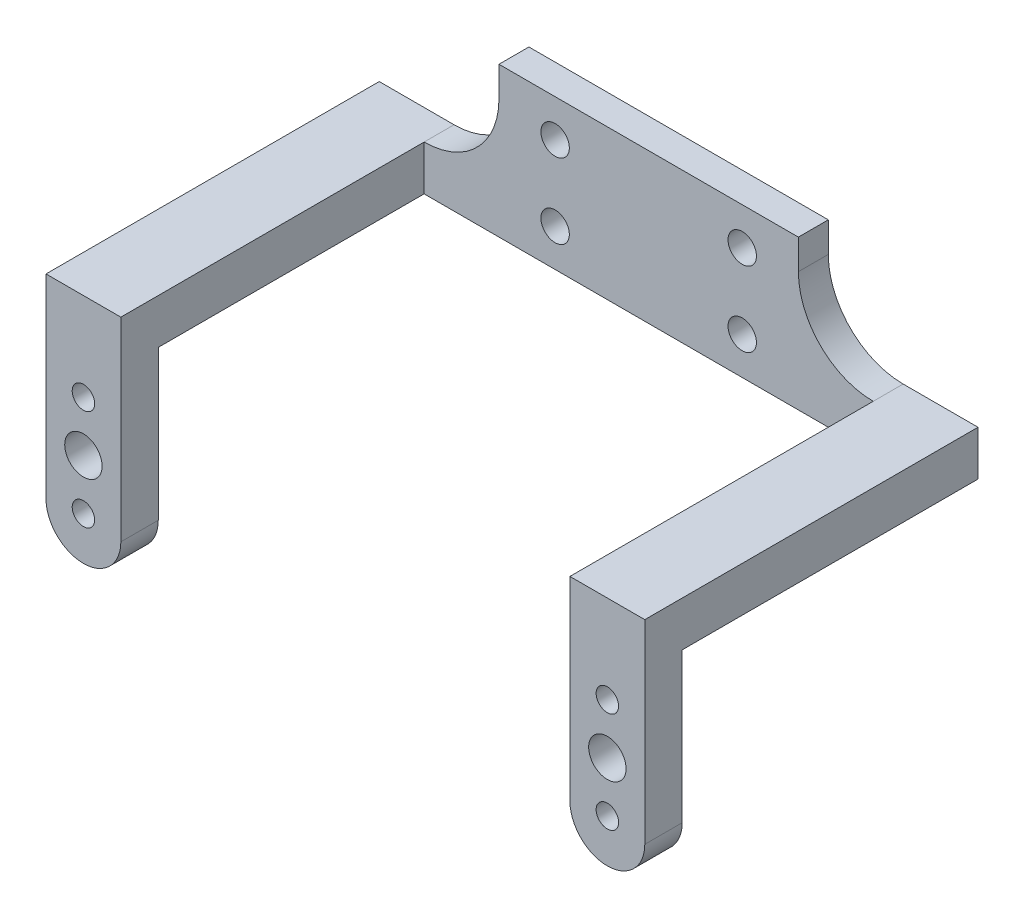
SolidWorks part; units mm, degrees
ref_plane "Front Plane" through (0, 0, 0) normal (0, 0, 1) x (1, 0, 0)
ref_plane "Top Plane" through (0, 0, 0) normal (0, 1, 0) x (1, 0, 0)
ref_plane "Right Plane" through (0, 0, 0) normal (1, 0, 0) x (0, 0, -1)
sketch "Sketch1" plane through (0, 0, 0) normal (0, 0, 1) x (1, 0, 0)
  line L0 (-12.5, 0) -> (-12.5, 20) construction
  line L1 (-20, 0) -> (20, 0)
  line L2 (-20, 0) -> (-20, 20)
  line L3 (-20, 20) -> (20, 20)
  line L4 (20, 0) -> (20, 20)
  line L5 (0, 0) -> (0, 20) construction
  line L6 (12.5, 0) -> (12.5, 20) construction
  line L7 (0, 10) -> (-20, 10) construction
  circle A0 centre (-12.5, 15) radius 1.9
  circle A1 centre (-12.5, 5) radius 1.9
  circle A2 centre (12.5, 5) radius 1.9
  circle A3 centre (12.5, 15) radius 1.9
  dimension "D2" = 3.8
  dimension "D1" = 10
  dimension "D3" = 25
  dimension "D4" = 40
  dimension "D5" = 20
extrude "main mounting" add sketch "Sketch1" along normal blind 4
sketch "Sketch2" plane through (0, 0, 0) normal (0, 0, -1) x (-1, 0, 0)
  line L0 (0, 0) -> (0, 20) construction
  line L1 (20, 0) -> (-20, 0) construction
  line L2 (-20, 20) -> (20, 20) construction
  line L3 (20, 0) -> (40, 0)
  line L4 (40, 0) -> (40, 20)
  line L5 (40, 20) -> (20, 20)
  line L6 (-40, 20) -> (-20, 20)
  line L7 (-40, 0) -> (-40, 20)
  line L8 (-20, 0) -> (-40, 0)
  line L9 (-20, 0) -> (-20, 20) construction
  line L10 (20, 20) -> (20, 0) construction
  line L11 (-20, 0) -> (-20, 20)
  line L12 (20, 20) -> (20, 0)
  dimension "D1" = 20
extrude "extention" add sketch "Sketch2" against normal up to surface (4 mm away) up to face at (10.6, 5, 4)
sketch "Sketch3" plane through (0, 0, 4) normal (0, 0, 1) x (1, 0, 0)
  line L0 (0, 0) -> (0, 20) construction
  line L1 (-40, 0) -> (40, 0) construction
  line L2 (40, 20) -> (-40, 20) construction
  line L3 (-30, 0) -> (-30, 6)
  line L4 (40, 0) -> (30, 0)
  line L5 (40, 0) -> (40, 6)
  line L6 (40, 6) -> (30, 6)
  line L7 (30, 0) -> (30, 6)
  line L8 (-40, 6) -> (-30, 6)
  line L9 (-40, 0) -> (-40, 6)
  line L10 (-40, 0) -> (-30, 0)
  dimension "D1" = 10
  dimension "D2" = 6
extrude "Boss-Extrude3" add sketch "Sketch3" along normal blind 40.52
sketch "Sketch4" plane through (0, 0, 0) normal (0, -1, 0) x (1, 0, 0)
  line L0 (-40, 44.52) -> (-40, 0) construction
  line L1 (-30, 44.52) -> (-40, 44.52)
  line L2 (-30, 44.52) -> (-30, 39.52)
  line L3 (-30, 39.52) -> (-40, 39.52)
  line L4 (-40, 44.52) -> (-40, 39.52)
  line L5 (0, 0) -> (0, 26.4175) construction
  line L6 (40, 44.52) -> (40, 39.52)
  line L7 (30, 39.52) -> (40, 39.52)
  line L8 (30, 44.52) -> (30, 39.52)
  line L9 (30, 44.52) -> (40, 44.52)
  dimension "D1" = 5
extrude "Boss-Extrude4" add sketch "Sketch4" along normal blind 25
sketch "Sketch5" plane through (0, 0, 39.52) normal (0, 0, 1) x (-1, 0, 0)
  line L0 (-22.5683, 12.5) -> (22.5683, 12.5) construction
  line L3 (0, 12.5) -> (0, 0) construction
  line L5 (-35, 12.5) -> (-35, 15) construction
  line L6 (35, 12.5) -> (35, 15) construction
  line L7 (-35, 25) -> (-35, 12.5) construction
  line L8 (-40, 25) -> (-30, 25) construction
  line L9 (-35, 12.5) -> (-35, -6) construction
  line L10 (-40, -6) -> (-30, -6) construction
  line L11 (-35, 12.5) -> (-40, 12.5) construction
  line L13 (-40, 25) -> (-40, 0) construction
  circle A0 centre (35, 19.23) radius 1.5
  circle A1 centre (35, 5.77) radius 1.5
  circle A2 centre (-35, 12.5) radius 2.5
  circle A7 centre (35, 12.5) radius 2.5
  circle A10 centre (-35, 5.77) radius 1.5
  circle A11 centre (-35, 19.23) radius 1.5
  dimension "D3" = 5
  dimension "D4" = 3
  dimension "D5" = 13.46
extrude "Cut-Extrude1" cut sketch "Sketch5" along normal through all
sketch "Sketch7" plane through (0, 0, 4) normal (0, 0, 1) x (1, 0, 0)
  line L0 (40, 20) -> (-40, 20) construction
  line L1 (-40, 6) -> (-20, 6)
  line L2 (-40, 6) -> (-40, 20)
  line L3 (-40, 20) -> (-20, 20)
  line L4 (-20, 6) -> (-20, 20)
  line L5 (0, 0) -> (0, 20) construction
  line L6 (-30, 0) -> (30, 0) construction
  line L7 (20, 6) -> (20, 20)
  line L8 (40, 20) -> (20, 20)
  line L9 (40, 6) -> (40, 20)
  line L10 (40, 6) -> (20, 6)
  dimension "D1" = 40
extrude "Cut-Extrude2" cut sketch "Sketch7" against normal through all
fillet "Fillet1" radius 10 2 edges at (20, 6, 2) (-20, 6, 2)
fillet "Fillet2" radius 5 4 edges at (40, -25, 42.02) (30, -25, 42.02) (-40, -25, 42.02) (-30, -25, 42.02)
